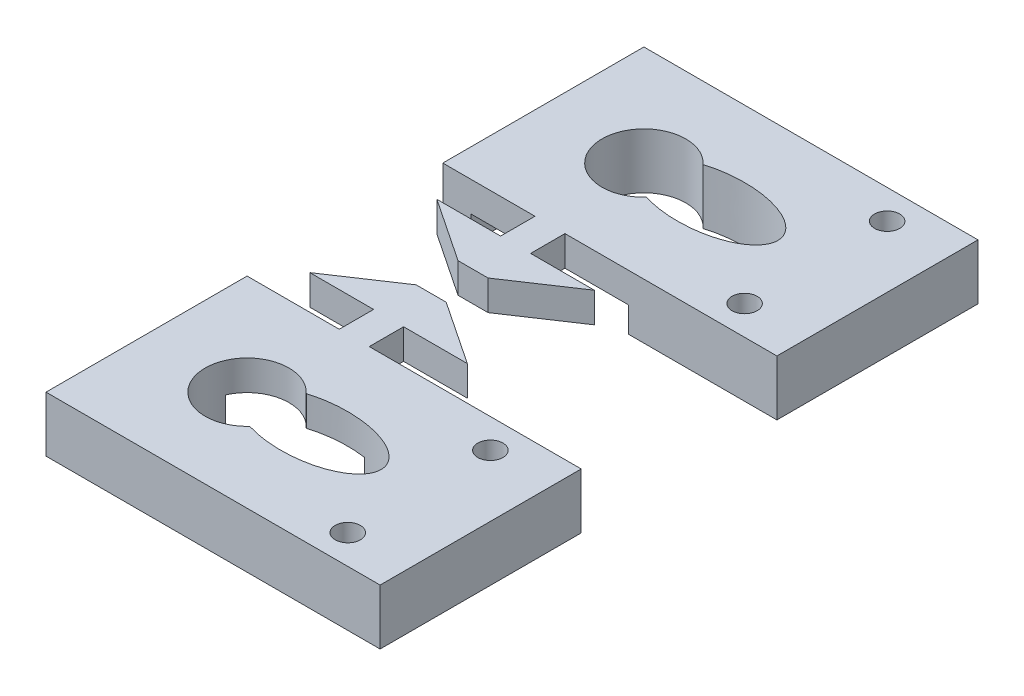
SolidWorks part; units mm, degrees
ref_plane "Front" through (0, 0, 0) normal (0, 0, 1) x (1, 0, 0)
ref_plane "Top" through (0, 0, 0) normal (0, 1, 0) x (1, 0, 0)
ref_plane "Right" through (0, 0, 0) normal (1, 0, 0) x (0, 0, -1)
sketch "Sketch1" plane through (0, 0, 0) normal (0, 1, 0) x (1, 0, 0)
  line L0 (-1.7907, 2.05) -> (-9.398, 2.05)
  line L2 (-1.7907, -2.05) -> (-1.7907, 2.05)
  line L4 (1.7907, -2.05) -> (1.7907, 2.05)
  line L7 (-9.398, 2.05) -> (-1.7907, 7.13)
  line L8 (-1.7907, 7.13) -> (1.7907, 7.13)
  line L9 (1.7907, 7.13) -> (9.398, 2.05)
  line L10 (9.398, 2.05) -> (1.7907, 2.05)
  line L11 (1.7907, -2.05) -> (27.088, -2.05)
  line L12 (-1.7907, -2.05) -> (-12.79, -2.05)
  line L13 (-12.79, -2.05) -> (-12.79, -26.05)
  line L14 (-12.79, -26.05) -> (27.088, -26.05)
  line L15 (27.088, -26.05) -> (27.088, -2.05)
  line L16 (27.088, -2.05) -> (1.7907, -2.05)
  point P0 (0, 0)
  point P17 (0, 7.13)
  point P24 (1.7907, 0)
  dimension "D1" = 18.796
  dimension "D2" = 3.5814
  dimension "D3" = 39.878
  dimension "D4" = 24
  dimension "D5" = 5.08
  dimension "D6" = 12.79
  dimension "D7" = 4.1
extrude "Boss-Extrude1" add sketch "Sketch1" along normal blind 3.5814 contours L14 L15 L11 L4 L10 L9 L8 L7 L0 L2 L12 L13 region at (6.6519, 0, 12.8512)
ref_plane "Plane1" through (0, 1.7907, 0) normal (0, 1, 0) x (1, 0, 0)
sketch "Sketch7" plane through (0, 0, 0) normal (0, 1, 0) x (1, 0, 0)
  line L1 (-12.79, -2.05) -> (27.088, -2.05)
  line L2 (-12.79, -2.05) -> (-12.79, -26.05)
  line L3 (-12.79, -26.05) -> (27.088, -26.05)
  line L4 (27.088, -2.05) -> (27.088, -26.05)
extrude "Boss-Extrude2" add sketch "Sketch7" along normal blind 3.035 and the other way blind 3.035
sketch "Sketch5" plane through (0, 3.5814, 0) normal (0, 1, 0) x (1, 0, 0)
  line L0 (-12.79, -2.05) -> (-12.79, -26.05) construction
  line L1 (-12.79, -14.05) -> (27.088, -14.05) construction
  line L2 (27.088, -26.05) -> (27.088, -2.05) construction
  circle A0 centre (-0.79, -14.05) radius 5
  circle A1 centre (19.738, -22.559) radius 1.5
  circle A2 centre (19.738, -5.541) radius 1.5
  ellipse E0 centre (7.21, -14.05) end of major axis (-0.79, -14.05) minor radius 4
  point P5 (-12.79, -14.05)
  dimension "D2" = 10
  dimension "D6" = 3
  dimension "D1" = 12
  dimension "D3" = 8
  dimension "D4" = 16
  dimension "D5" = 17.018
  dimension "D7" = 7.35
extrude "Cut-Extrude3" cut sketch "Sketch5" against normal through all both and the other way through all contours A0 L1 E0 | E0 L1 A0 | A0 L1 E0 | L1 A0 E0 | L1 E0 A0 | L1 A0 E0 | A1 | A2 region at (1.9147, 3.5814, 12.7418) region at (-1.952, 3.5814, 16.5217) region at (1.9147, 3.5814, 15.3582) region at (-1.952, 3.5814, 11.5783) region at (8.8346, 3.5814, 12.2329) region at (8.8346, 3.5814, 15.8671) region at (19.738, 3.5814, 22.559)
ref_plane "Plane2" through (0, 0, -17.13) normal (0, 0, -1) x (-1, 0, 0)
sketch "Sketch8" plane through (0, 0, 2.05) normal (0, 0, -1) x (-1, 0, 0)
  line L0 (-27.088, -3.035) -> (12.79, -3.035) construction
  line L1 (-9.398, 0) -> (9.398, 0)
  line L2 (-9.398, 0) -> (-9.398, -3.035)
  line L3 (-9.398, -3.035) -> (9.398, -3.035)
  line L4 (9.398, 0) -> (9.398, -3.035)
  line L5 (-9.398, 3.5814) -> (-9.398, 0) construction
  line L6 (9.398, 3.5814) -> (9.398, 0) construction
  line L7 (-1.7907, 0) -> (1.7907, 0) construction
extrude "Cut-Extrude4" cut sketch "Sketch8" against normal blind 10
ref_plane "Plane3" through (0, 0, -9.63) normal (0, 0, -1) x (-1, 0, 0)
mirror "Mirror2" about plane through (0, 0, -9.63) normal (0, 0, -1) of bodies 108
sketch "Sketch9" plane through (0, -3.035, 0) normal (0, -1, 0) x (-1, 0, 0)
  line L0 (-24.088, 38.31) -> (-24.088, 28.31) construction
  line L1 (-27.088, 45.31) -> (-27.088, 21.31) construction
  text T0 "Lt."
  point P3 (-24.088, 33.31)
  point P6 (-27.088, 33.31)
  dimension "D1" = 10
  dimension "D2" = 3
extrude "Cut-Extrude5" cut sketch "Sketch9" against normal blind 2
sketch "Sketch10" plane through (0, -3.035, 0) normal (0, -1, 0) x (1, 0, 0)
  line L0 (24.088, 19.55) -> (24.088, 8.55) construction
  line L1 (27.088, 26.05) -> (27.088, 2.05) construction
  text T0 "Rt."
  point P4 (27.088, 14.05)
  point P5 (24.088, 14.05)
  dimension "D1" = 11
  dimension "D2" = 3
extrude "Cut-Extrude6" cut sketch "Sketch10" against normal blind 2
